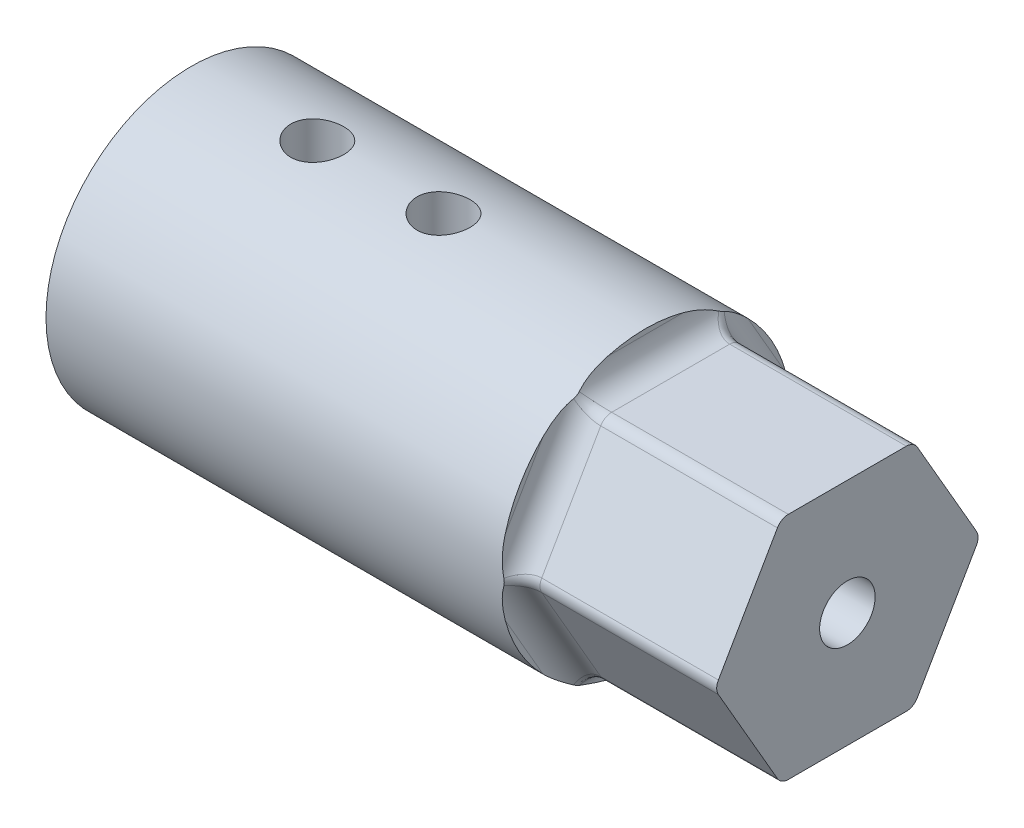
SolidWorks part; units mm, degrees
material "PLA2"
ref_plane "Front Plane" through (0, 0, 0) normal (0, 0, 1) x (1, 0, 0)
ref_plane "Top Plane" through (0, 0, 0) normal (0, 1, 0) x (1, 0, 0)
ref_plane "Right Plane" through (0, 0, 0) normal (1, 0, 0) x (0, 0, -1)
sketch "Sketch1" plane through (0, 0, 0) normal (1, 0, 0) x (0, 0, -1)
  line L0 (0, 0) -> (50000, 0) construction
  line L1 (-3.3362, 5.7785) -> (3.3362, 5.7785)
  line L2 (3.3362, 5.7785) -> (6.6724, 0)
  line L3 (0, 0) -> (0, 50000) construction
  line L4 (-3.3362, 5.7785) -> (-6.6724, 0)
  line L5 (-3.3362, -5.7785) -> (-6.6724, 0)
  line L6 (3.3362, -5.7785) -> (6.6724, 0)
  line L7 (-3.3362, -5.7785) -> (3.3362, -5.7785)
  point P8 (0, 5.7785)
  point P13 (0, -5.7785)
  dimension "D1" = 11.557
  dimension "D2" = 11.557
extrude "Hex" add sketch "Sketch1" along normal blind 10.16
sketch "Sketch2" plane through (0, 0, 0) normal (-1, 0, 0) x (0, 0, 1)
  circle A0 centre (0, 0) radius 7.3025
  circle A1 centre (0, 0) radius 3.2766
  dimension "D1" = 6.5532
  dimension "D2" = 14.605
extrude "Rotary_Shaft" add sketch "Sketch2" along normal blind 22.86
fillet "Fillet1" radius 1.27 6 edges at (0, 2.8893, 5.0043) (0, -2.8893, 5.0043) (0, -5.7785, 0) (0, -2.8893, -5.0043) (0, 2.8893, -5.0043) (0, 5.7785, 0)
fillet "Fillet2" radius 0.635 12 edges at (0.6814, 5.9232, 3.4197) (0.6814, 0, 6.8395) (0.6814, -5.9232, 3.4197) (0.6814, 5.9232, -3.4197) (0.6814, -5.9232, -3.4197) (0.6814, 0, -6.8395) (5.715, 5.7785, 3.3362) (5.715, 0, 6.6724) (5.715, -5.7785, 3.3362) (5.715, 5.7785, -3.3362) (5.715, -5.7785, -3.3362) (5.715, 0, -6.6724)
fillet "Fillet3" radius 0.508 1 edges at (0, 0, 3.2766)
sketch "Sketch3" plane through (0, 0, 0) normal (0, 1, 0) x (1, 0, 0)
  line L0 (-22.86, -7.3025) -> (0.1986, -7.3025) construction
  line L1 (-22.86, 7.3025) -> (-22.86, -7.3025) construction
  line L2 (0.1986, 7.3025) -> (-22.86, 7.3025) construction
  line L3 (-22.86, -7.3025) -> (0.1986, -7.3025) construction
  line L4 (-22.86, 7.3025) -> (-22.86, -7.3025) construction
  line L5 (0.1986, 7.3025) -> (-22.86, 7.3025) construction
  line L6 (-22.86, 0) -> (0, 0) construction
  circle A0 centre (-16.51, 0) radius 1.3335
  circle A1 centre (-10.16, 0) radius 1.3335
  dimension "D1" = 2.667
  dimension "D2" = 2.667
  dimension "D3" = 6.35
  dimension "D4" = 6.35
extrude "Cut-Extrude1" cut sketch "Sketch3" along normal through all
sketch "Sketch4" plane through (0, 0, 0) normal (-1, 0, 0) x (0, 0, 1)
  circle A0 centre (0, 0) radius 1.397
  dimension "D1" = 2.794
extrude "Cut-Extrude2" cut sketch "Sketch4" against normal through all
equation "\"D4@Sketch3\"=\"D3@Sketch3\""
equation "\"D2@Sketch3\"=\"D1@Sketch3\""
equation "\"D2@Sketch1\"=\"D1@Sketch1\""
